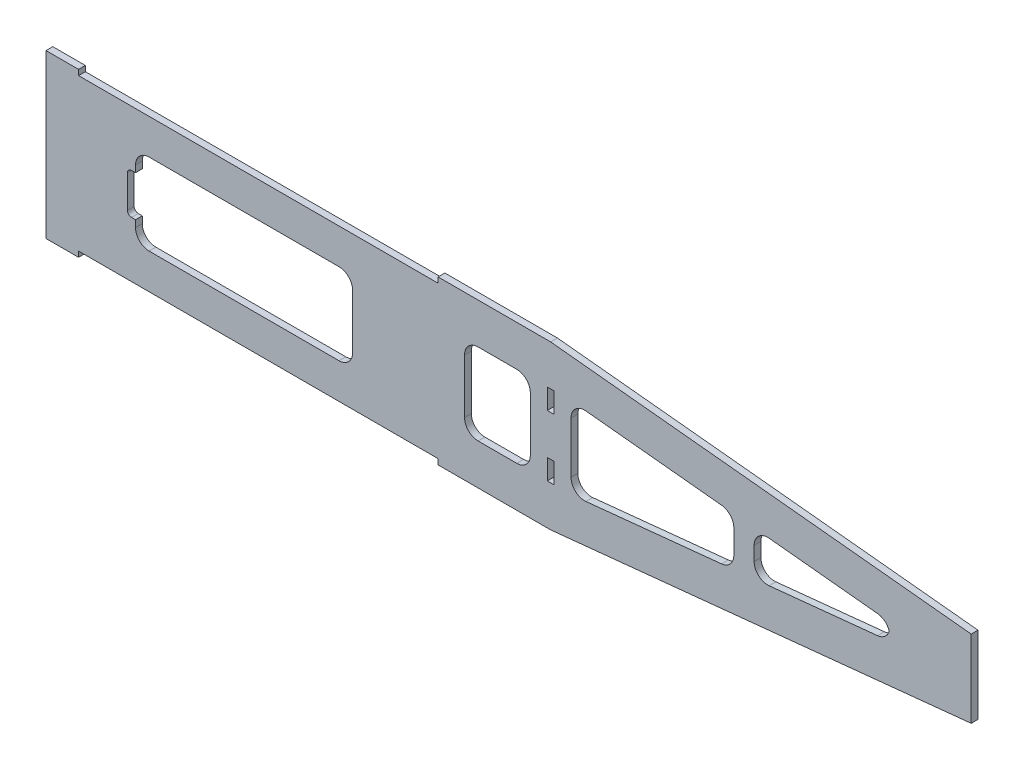
SolidWorks part; units mm, degrees
ref_plane "Ebene vorne" through (0, 0, 0) normal (0, 0, 1) x (1, 0, 0)
ref_plane "Ebene oben" through (0, 0, 0) normal (0, 1, 0) x (1, 0, 0)
ref_plane "Ebene rechts" through (0, 0, 0) normal (1, 0, 0) x (0, 0, -1)
sketch "Skizze1" plane through (0, 0, 0) normal (0, 0, 1) x (1, 0, 0)
  line L0 (0, 0) -> (682, 0) construction
  line L1 (0, 60) -> (0, -60)
  line L2 (0, -60) -> (372, -60)
  line L3 (372, -60) -> (682, -28.5)
  line L4 (682, -28.5) -> (682, 28.5)
  line L5 (372, 60) -> (682, 28.5)
  line L6 (0, 60) -> (372, 60)
  dimension "D1" = 682
  dimension "D2" = 120
  dimension "D3" = 57
  dimension "D4" = 310
extrude "Grundplatte" add sketch "Skizze1" along normal blind 5
sketch "Skizze2" plane through (0, 0, 5) normal (0, 0, 1) x (1, 0, 0)
  line L0 (50, 0) -> (60, 0) construction
  line L1 (226, 30) -> (66, 30)
  line L2 (226, 30) -> (226, -30)
  line L3 (226, -30) -> (66, -30)
  line L4 (66, 30) -> (66, 15)
  line L5 (226, 30) -> (66, -30) construction
  line L6 (226, -30) -> (66, 30) construction
  line L7 (60, -15) -> (60, 15)
  line L8 (60, 15) -> (66, 15)
  line L9 (60, -15) -> (66, -15)
  line L10 (66, -15) -> (66, -30)
  line L11 (0, 60) -> (0, -60) construction
  point P0 (146, 0)
  dimension "D1" = 60
  dimension "D2" = 60
  dimension "D3" = 160
  dimension "D4" = 30
  dimension "D5" = 6
extrude "Schnitt-Linear austragen1" cut sketch "Skizze2" against normal through all
fillet "Verrundung1" radius 10 4 edges at (226, 30, 2.5) (226, -30, 2.5) (66, 30, 2.5) (66, -30, 2.5)
sketch "Skizze3" plane through (0, 0, 5) normal (0, 0, 1) x (1, 0, 0)
  line L0 (0, 0) -> (682, 0) construction
  line L1 (0, 60) -> (0, -60) construction
  line L2 (682, -28.5) -> (682, 28.5) construction
  line L3 (372, 60) -> (0, 60) construction
  line L4 (24, 60) -> (289, 60)
  line L5 (24, 60) -> (24, 56)
  line L6 (24, 56) -> (289, 56)
  line L7 (289, 60) -> (289, 56)
  line L8 (289, -60) -> (289, -56)
  line L9 (24, -56) -> (289, -56)
  line L10 (24, -60) -> (24, -56)
  line L11 (24, -60) -> (289, -60)
  dimension "D1" = 4
  dimension "D2" = 265
  dimension "D3" = 24
extrude "Ausschnitt_Flächenaufdoppler" cut sketch "Skizze3" against normal through all
sketch "Skizze4" plane through (0, 0, 5) normal (0, 0, 1) x (1, 0, 0)
  line L0 (0, 0) -> (308.519, 0.0258) construction
  line L5 (308.519, -29.9742) -> (308.519, 30.0258)
  line L6 (387, -29.9742) -> (387, 30.0258)
  line L7 (387, 30.0258) -> (507, 17.8323)
  line L8 (507, 17.8323) -> (507, -17.7806)
  line L9 (387, -29.9742) -> (507, -17.7806)
  line L11 (682, 28.5) -> (372, 60) construction
  line L12 (308.519, 30.0258) -> (357, 30.0258)
  line L14 (357, 30.0258) -> (357, -29.9742)
  line L15 (308.519, -29.9742) -> (357, -29.9742)
  line L16 (522, -16.2564) -> (522, 16.3081)
  line L17 (522, 16.3081) -> (622, 6.1468)
  line L18 (622, 6.1468) -> (622, -6.0951)
  line L19 (522, -16.2564) -> (622, -6.0951)
  line L20 (357, 0.0258) -> (372, 0.0258) construction
  line L21 (372, 0.0258) -> (387, 0.0258) construction
  line L22 (372, -60) -> (372, 0.0258) construction
  line L23 (0, 60) -> (0, -60) construction
  line L24 (308.519, 0.0258) -> (357, 0.0258) construction
  point P14 (507, 0.0258)
  point P16 (357, 0.0258)
  point P17 (308.519, 0.0258)
  point P24 (622, 0.0258)
  point P25 (522, 0.0258)
  dimension "D1" = 30
  dimension "D2" = 60
  dimension "D3" = 120
  dimension "D4" = 15
  dimension "D5" = 100
extrude "Ausschnitt Gewicht" cut sketch "Skizze4" against normal through all
fillet "Verrundung2" radius 10 12 edges at (387, -29.9742, 2.5) (387, 30.0258, 2.5) (357, -29.9742, 2.5) (308.519, -29.9742, 2.5) (308.519, 30.0258, 2.5) (357, 30.0258, 2.5) (622, 6.1468, 2.5) (622, -6.0951, 2.5) (522, 16.3081, 2.5) (522, -16.2564, 2.5) (507, -17.7806, 2.5) (507, 17.8323, 2.5)
fillet "Verrundung4" radius 3 2 edges at (60, -15, 2.5) (60, 15, 2.5)
sketch "Skizze5" plane through (0, 0, 5) normal (0, 0, 1) x (1, 0, 0)
  line L0 (372, 60) -> (372, 22.5) construction
  line L1 (372, 22.5) -> (372, -22.5) construction
  line L2 (372, -22.5) -> (372, -60) construction
  line L4 (374.5, 30) -> (369.5, 30)
  line L5 (374.5, 30) -> (374.5, 15)
  line L6 (374.5, 15) -> (369.5, 15)
  line L7 (369.5, 30) -> (369.5, 15)
  line L8 (374.5, 30) -> (369.5, 15) construction
  line L9 (374.5, 15) -> (369.5, 30) construction
  line L10 (374.5, -15) -> (369.5, -15)
  line L11 (374.5, -15) -> (374.5, -30)
  line L12 (374.5, -30) -> (369.5, -30)
  line L13 (369.5, -15) -> (369.5, -30)
  line L14 (374.5, -15) -> (369.5, -30) construction
  line L15 (374.5, -30) -> (369.5, -15) construction
  dimension "D1" = 30
  dimension "D2" = 5
  dimension "D3" = 15
extrude "Schnitt-Linear austragen2" cut sketch "Skizze5" against normal through all
